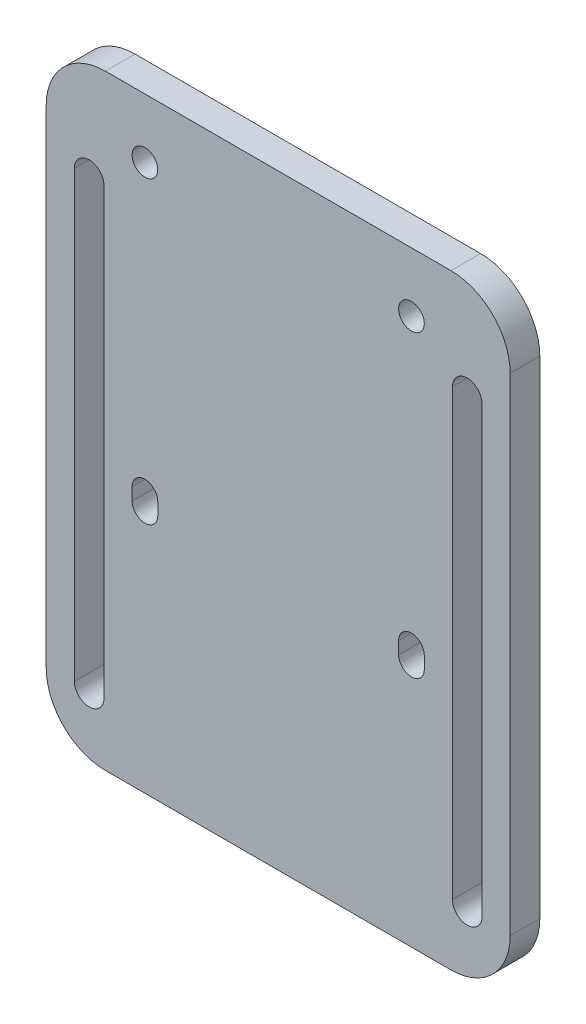
SolidWorks part; units mm, degrees
material "Acrylic (Medium-high impact)"
ref_plane "Спереди" through (0, 0, 0) normal (0, 0, 1) x (1, 0, 0)
ref_plane "Сверху" through (0, 0, 0) normal (0, 1, 0) x (1, 0, 0)
ref_plane "Справа" through (0, 0, 0) normal (1, 0, 0) x (0, 0, -1)
sketch "Model" plane through (0, 0, 0) normal (0, 0, 1) x (1, 0, 0)
  line L0 (0, 130.393) -> (0, -19.607) construction
  line L1 (38.3, 119.0065) -> (38.3, 3.8567) construction
  line L2 (39.6393, 110.7) -> (20.3566, 110.7) construction
  line L3 (27, 114.3973) -> (27, 106.7903) construction
  line L8 (27, 57.0366) -> (27, 46.0463) construction
  line L14 (-27, 114.3973) -> (-27, 106.7903) construction
  line L15 (-39.6393, 110.7) -> (-20.3566, 110.7) construction
  line L16 (-29.6, 50) -> (-29.6, 52.5)
  line L17 (-29.6, 52.5) -> (-29.6, 50)
  line L18 (-27, 57.0366) -> (-27, 46.0463) construction
  line L19 (-24.4, 52.5) -> (-24.4, 50)
  line L20 (-24.4, 50) -> (-24.4, 52.5)
  line L22 (-41.3, 12.5) -> (-41.3, 102.5)
  line L23 (-41.3, 102.5) -> (-41.3, 12.5)
  line L24 (-38.3, 119.0065) -> (-38.3, 3.8567) construction
  line L25 (-35.3, 102.5) -> (-35.3, 12.5)
  line L26 (-35.3, 12.5) -> (-35.3, 102.5)
  line L29 (-41.3, 12.5) -> (-35.3, 12.5) construction
  line L2974 (29.6, 52.5) -> (29.6, 50)
  line L2987 (24.4, 50) -> (24.4, 52.5)
  line L2994 (35.3, 12.5) -> (35.3, 102.5)
  line L3007 (41.3, 102.5) -> (41.3, 12.5)
  line L3504 (35, 0) -> (-35, 0)
  line L3511 (-47, 12) -> (-47, 110.7)
  line L3518 (-35, 122.7) -> (35, 122.7)
  line L3525 (47, 110.7) -> (47, 12)
  line L3777 (24.4, 52.5) -> (24.4, 50)
  line L3790 (29.6, 50) -> (29.6, 52.5)
  line L3887 (41.3, 12.5) -> (41.3, 102.5)
  line L3900 (35.3, 102.5) -> (35.3, 12.5)
  arc A0 (-47, 12) -> (-35, 0) centre (-35, 12) ccw
  arc A1 (35, 0) -> (47, 12) centre (35, 12) ccw
  arc A2 (47, 110.7) -> (35, 122.7) centre (35, 110.7) ccw
  arc A3 (-47, 110.7) -> (-35, 122.7) centre (-35, 110.7) cw
  circle A8 centre (27, 110.7) radius 2.6
  arc A9 (24.4, 52.5) -> (29.6, 52.5) centre (27, 52.5) cw
  arc A10 (24.4, 50) -> (29.6, 50) centre (27, 50) ccw
  arc A11 (35.3, 12.5) -> (41.3, 12.5) centre (38.3, 12.5) ccw
  arc A12 (35.3, 102.5) -> (41.3, 102.5) centre (38.3, 102.5) cw
  arc A17 (-35.3, 102.5) -> (-41.3, 102.5) centre (-38.3, 102.5) ccw
  circle A18 centre (-27, 110.7) radius 2.6
  arc A19 (-24.4, 50) -> (-29.6, 50) centre (-27, 50) cw
  arc A20 (-24.4, 52.5) -> (-29.6, 52.5) centre (-27, 52.5) ccw
  arc A22 (-35.3, 12.5) -> (-41.3, 12.5) centre (-38.3, 12.5) cw
  point P18 (0, 0)
  point P21 (0, 0)
  dimension "D1" = 12
  dimension "D17" = 5.2
  dimension "D22" = 2.6
  dimension "D23" = 2.6
  dimension "D26" = 90
  dimension "D6" = 54
  dimension "D2" = 70
  dimension "D3" = 122.7
  dimension "D4" = 76.6
  dimension "D5" = 58.2
  dimension "D7" = 54
  dimension "D20" = 2.5
  dimension "D21" = 5.2
  dimension "D24" = 50
  dimension "D25" = 6
  dimension "D27" = 12.5
extrude "Base" add sketch "Model" along normal blind 6 contours A3 L3511 A0 L3504 A1 L3525 A2 L3518 L25 A22 L22 A17 A20 L19 A19 L16 L2994 A12 L3007 A11 A8 A10 L2987 A9 L2974 region at (0, 61.6424, 0)
